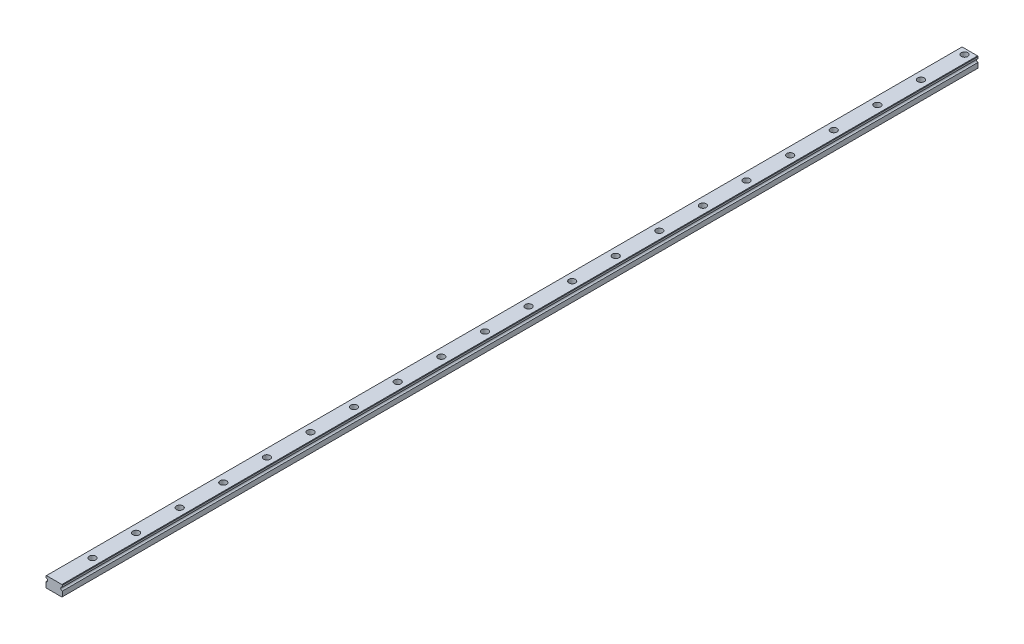
SolidWorks part; units mm, degrees
ref_plane "前视基准面" through (0, 0, 0) normal (0, 0, 1) x (1, 0, 0)
ref_plane "上视基准面" through (0, 0, 0) normal (0, 1, 0) x (1, 0, 0)
ref_plane "右视基准面" through (0, 0, 0) normal (1, 0, 0) x (0, 0, -1)
other "Configuration Table"
sketch "草图1" plane through (0, 0, 0) normal (0, 0, 1) x (1, 0, 0)
  line L0 (-7.6432, 0.2342) -> (-7.6432, -4.3658)
  line L1 (-7.6432, -4.3658) -> (-7.2432, -4.7658)
  line L2 (-7.2432, -4.7658) -> (6.9568, -4.7658)
  line L3 (6.9568, -4.7658) -> (7.3568, -4.3658)
  line L4 (7.3568, -4.3658) -> (7.3568, 0.2342)
  line L5 (7.3568, 3.2342) -> (7.3568, 4.8342)
  line L6 (7.3568, 4.8342) -> (6.9568, 5.2342)
  line L7 (6.9568, 5.2342) -> (-7.2432, 5.2342)
  line L8 (-7.2432, 5.2342) -> (-7.6432, 4.8342)
  line L9 (-7.6432, 4.8342) -> (-7.6432, 3.2342)
  arc A0 (5.8568, 1.7342) -> (7.3568, 0.2342) centre (7.3568, 1.7342) ccw
  arc A1 (7.3568, 3.2342) -> (5.8568, 1.7342) centre (7.3568, 1.7342) ccw
  arc A2 (-7.6432, 0.2342) -> (-7.6432, 3.2342) centre (-7.6432, 1.7342) ccw
extrude "凸台-拉伸1" add sketch "草图1" along normal blind 1000
sketch "草图2" plane through (0, 5.2342, 0) normal (0, 1, 0) x (1, 0, 0)
  circle A0 centre (0, -4.969) radius 1.5
  dimension "D1" = 3
extrude "切除-拉伸1" cut sketch "草图2" against normal blind 20
sketch "草图3" plane through (0, 5.2342, 0) normal (0, 1, 0) x (1, 0, 0)
  circle A0 centre (0, -4.969) radius 3
  dimension "D1" = 6
extrude "切除-拉伸2" cut sketch "草图3" against normal blind 4.5
sketch "草图4" plane through (0, 5.2342, 0) normal (0, 1, 0) x (1, 0, 0)
  line L0 (0, 0) -> (0, -1341.5051) construction
pattern_linear "阵列(线性)1" count 25 spacing 40 along (0, 0, 1) of "切除-拉伸2", "切除-拉伸1"
sketch "草图5" plane through (0, 0, 1000) normal (0, 0, 1) x (1, 0, 0)
  line L10 (-7.6432, 0.2342) -> (-7.6432, -4.3658)
  line L11 (-7.6432, -4.3658) -> (-7.2432, -4.7658)
  line L12 (-7.2432, -4.7658) -> (6.9568, -4.7658)
  line L13 (6.9568, -4.7658) -> (7.3568, -4.3658)
  line L14 (7.3568, -4.3658) -> (7.3568, 0.2342)
  line L15 (7.3568, 3.2342) -> (7.3568, 4.8342)
  line L16 (7.3568, 4.8342) -> (6.9568, 5.2342)
  line L17 (6.9568, 5.2342) -> (-7.2432, 5.2342)
  line L18 (-7.2432, 5.2342) -> (-7.6432, 4.8342)
  line L19 (-7.6432, 4.8342) -> (-7.6432, 3.2342)
  line L20 (-7.6432, 0.2342) -> (-7.6432, -4.3658)
  line L21 (-7.6432, -4.3658) -> (-7.2432, -4.7658)
  line L22 (-7.2432, -4.7658) -> (6.9568, -4.7658)
  line L23 (6.9568, -4.7658) -> (7.3568, -4.3658)
  line L24 (7.3568, -4.3658) -> (7.3568, 0.2342)
  line L25 (7.3568, 3.2342) -> (7.3568, 4.8342)
  line L26 (7.3568, 4.8342) -> (6.9568, 5.2342)
  line L27 (6.9568, 5.2342) -> (-7.2432, 5.2342)
  line L28 (-7.2432, 5.2342) -> (-7.6432, 4.8342)
  line L29 (-7.6432, 4.8342) -> (-7.6432, 3.2342)
  arc A2 (-7.6432, 0.2342) -> (-7.6432, 3.2342) centre (-7.6432, 1.7342) ccw
  arc A3 (7.3568, 3.2342) -> (7.3568, 0.2342) centre (7.3568, 1.7342) ccw
  arc A4 (-7.6432, 0.2342) -> (-7.6432, 3.2342) centre (-7.6432, 1.7342) ccw
  arc A5 (7.3568, 3.2342) -> (7.3568, 0.2342) centre (7.3568, 1.7342) ccw
  dimension "D1" = 0
sketch "草图6" plane through (0, 0, 0) normal (0, 0, -1) x (-1, 0, 0)
  line L10 (7.6432, 3.2342) -> (7.6432, 4.8342)
  line L11 (7.6432, 4.8342) -> (7.2432, 5.2342)
  line L12 (7.2432, 5.2342) -> (-6.9568, 5.2342)
  line L13 (-6.9568, 5.2342) -> (-7.3568, 4.8342)
  line L14 (-7.3568, 4.8342) -> (-7.3568, 3.2342)
  line L15 (-7.3568, 0.2342) -> (-7.3568, -4.3658)
  line L16 (-7.3568, -4.3658) -> (-6.9568, -4.7658)
  line L17 (-6.9568, -4.7658) -> (7.2432, -4.7658)
  line L18 (7.2432, -4.7658) -> (7.6432, -4.3658)
  line L19 (7.6432, -4.3658) -> (7.6432, 0.2342)
  line L20 (7.6432, 3.2342) -> (7.6432, 4.8342)
  line L21 (7.6432, 4.8342) -> (7.2432, 5.2342)
  line L22 (7.2432, 5.2342) -> (-6.9568, 5.2342)
  line L23 (-6.9568, 5.2342) -> (-7.3568, 4.8342)
  line L24 (-7.3568, 4.8342) -> (-7.3568, 3.2342)
  line L25 (-7.3568, 0.2342) -> (-7.3568, -4.3658)
  line L26 (-7.3568, -4.3658) -> (-6.9568, -4.7658)
  line L27 (-6.9568, -4.7658) -> (7.2432, -4.7658)
  line L28 (7.2432, -4.7658) -> (7.6432, -4.3658)
  line L29 (7.6432, -4.3658) -> (7.6432, 0.2342)
  arc A2 (7.6432, 3.2342) -> (7.6432, 0.2342) centre (7.6432, 1.7342) ccw
  arc A3 (-7.3568, 0.2342) -> (-7.3568, 3.2342) centre (-7.3568, 1.7342) ccw
  arc A4 (7.6432, 3.2342) -> (7.6432, 0.2342) centre (7.6432, 1.7342) ccw
  arc A5 (-7.3568, 0.2342) -> (-7.3568, 3.2342) centre (-7.3568, 1.7342) ccw
  dimension "D1" = 0
extrude "切除-拉伸4" cut sketch "草图6" against normal blind 80
sketch "草图7" plane through (0, 0, 80) normal (0, 0, -1) x (-1, 0, 0)
  line L10 (7.6432, 3.2342) -> (7.6432, 4.8342)
  line L11 (7.6432, 4.8342) -> (7.2432, 5.2342)
  line L12 (7.2432, 5.2342) -> (-6.9568, 5.2342)
  line L13 (-6.9568, 5.2342) -> (-7.3568, 4.8342)
  line L14 (-7.3568, 4.8342) -> (-7.3568, 3.2342)
  line L15 (-7.3568, 0.2342) -> (-7.3568, -4.3658)
  line L16 (-7.3568, -4.3658) -> (-6.9568, -4.7658)
  line L17 (-6.9568, -4.7658) -> (7.2432, -4.7658)
  line L18 (7.2432, -4.7658) -> (7.6432, -4.3658)
  line L19 (7.6432, -4.3658) -> (7.6432, 0.2342)
  line L20 (7.6432, 3.2342) -> (7.6432, 4.8342)
  line L21 (7.6432, 4.8342) -> (7.2432, 5.2342)
  line L22 (7.2432, 5.2342) -> (-6.9568, 5.2342)
  line L23 (-6.9568, 5.2342) -> (-7.3568, 4.8342)
  line L24 (-7.3568, 4.8342) -> (-7.3568, 3.2342)
  line L25 (-7.3568, 0.2342) -> (-7.3568, -4.3658)
  line L26 (-7.3568, -4.3658) -> (-6.9568, -4.7658)
  line L27 (-6.9568, -4.7658) -> (7.2432, -4.7658)
  line L28 (7.2432, -4.7658) -> (7.6432, -4.3658)
  line L29 (7.6432, -4.3658) -> (7.6432, 0.2342)
  arc A2 (7.6432, 3.2342) -> (7.6432, 0.2342) centre (7.6432, 1.7342) ccw
  arc A3 (-7.3568, 0.2342) -> (-7.3568, 3.2342) centre (-7.3568, 1.7342) ccw
  arc A4 (7.6432, 3.2342) -> (7.6432, 0.2342) centre (7.6432, 1.7342) ccw
  arc A5 (-7.3568, 0.2342) -> (-7.3568, 3.2342) centre (-7.3568, 1.7342) ccw
  dimension "D1" = 0
extrude "切除-拉伸5" cut sketch "草图7" against normal blind 80
